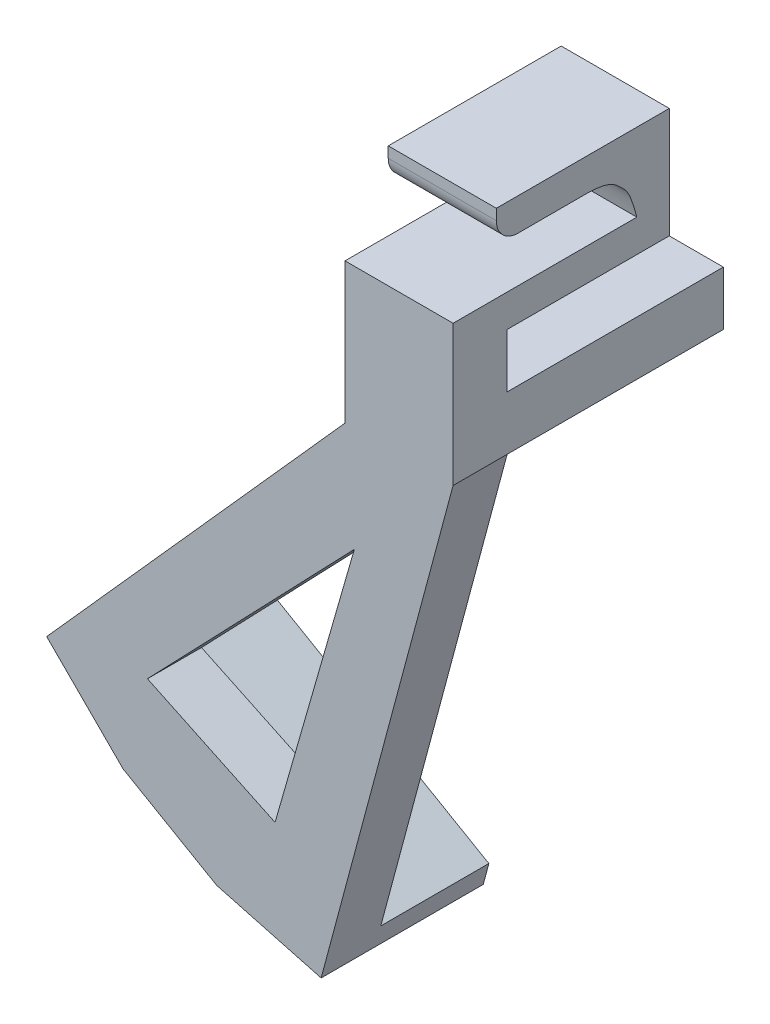
SolidWorks part; units mm, degrees
ref_plane "Front Plane" through (0, 0, 0) normal (0, 0, 1) x (1, 0, 0)
ref_plane "Top Plane" through (0, 0, 0) normal (0, 1, 0) x (1, 0, 0)
ref_plane "Right Plane" through (0, 0, 0) normal (1, 0, 0) x (0, 0, -1)
sketch "Sketch2" plane through (0, 0, 0) normal (1, 0, 0) x (0, 0, -1)
  line L0 (20, 13) -> (20, 20.213)
  line L1 (0, 0) -> (5, 0)
  line L2 (0, 0) -> (0, 13)
  line L3 (0, 13) -> (5, 13)
  line L4 (5, 0) -> (5, 13)
  line L6 (5, 0) -> (5, 3)
  line L9 (5, 13) -> (20, 13)
  line L10 (5, 13) -> (5, 10)
  line L11 (5, 10) -> (20, 10)
  line L12 (20, 13) -> (20, 10)
  line L13 (5, 5) -> (25, 5)
  line L14 (5, 5) -> (5, 0)
  line L15 (5, 0) -> (25, 0)
  line L16 (25, 5) -> (25, 0)
  line L17 (20, 20.213) -> (4, 20.213)
  line L18 (4, 20.213) -> (4, 19.213)
  line L19 (6, 17.213) -> (12.3497, 17.213)
  line L20 (17, 13) -> (20, 13)
  arc A0 (4, 19.213) -> (6, 17.213) centre (6, 19.213) ccw
  spline S0 degree 3 poles (12.3497, 17.213) (14.5346, 17.213) (15.6196, 15.8727) (16.3409, 15.5029) (17, 13) knots 0 0 0 0 0.495489 1 1 1 1
  point P24 (4, 17.213)
  dimension "D3" = 2
  dimension "D16" = 6.9797
  dimension "D1" = 13
  dimension "D2" = 3
  dimension "D4" = 3
  dimension "D5" = 4.213
  dimension "D6" = 5
  dimension "D7" = 3
  dimension "D8" = 5
  dimension "D9" = 15
  dimension "D10" = 20
  dimension "D14" = 2.9866
  dimension "D15" = 4.3328
extrude "Boss-Extrude1" add sketch "Sketch2" along normal blind 10 contours L1 L4 L3 L2 | L4 | L16 L13 L4 L15 | L12 L9 L4 L11 | L19 S0 L9 L0 L17 L18 A0 region at (0, 17.8441, -13.6548) region at (0, 11.5, -12.5) region at (0, 6.5, -2.5) region at (0, 2.5, -15)
sketch "Sketch4" plane through (0, 0, 0) normal (0, 0, 1) x (1, 0, 0)
  line L0 (10, 0) -> (-2.2086, -45.5631)
  line L1 (-2.2086, -45.5631) -> (-11.8678, -42.9749)
  line L2 (-11.8678, -42.9749) -> (-20.5281, -37.9749)
  line L3 (-20.5281, -37.9749) -> (-27.5992, -30.9038)
  line L4 (-27.5992, -30.9038) -> (0, 0)
  line L6 (0, 0) -> (10, 0)
  line L7 (10, 0) -> (0, 0) construction
  line L8 (10, 5) -> (-3.4586, -45.2281) construction
  line L9 (10, 5) -> (0, 5) construction
  line L10 (10, 0) -> (10, 13) construction
  line L11 (-18.2774, -29.6218) -> (-6.4709, -35.2264)
  line L12 (-6.4709, -35.2264) -> (0.8649, -9.6768)
  line L13 (0.8649, -9.6768) -> (-18.2774, -29.6218)
  dimension "D1" = 15
  dimension "D2" = 165
  dimension "D3" = 165
  dimension "D4" = 10
  dimension "D5" = 52
extrude "Boss-Extrude2" add sketch "Sketch4" against normal up to surface (5 mm away) up to face at (5, 7.5, -5)
sketch "Sketch5" plane through (0, 0, -5) normal (0, 0, -1) x (-1, 0, 0)
  line L0 (2.2086, -45.5631) -> (11.8678, -42.9749)
  line L1 (11.8678, -42.9749) -> (20.5281, -37.9749)
  line L2 (20.5281, -37.9749) -> (27.5992, -30.9038)
  line L3 (27.5992, -30.9038) -> (26.267, -29.4121)
  line L4 (27.5992, -30.9038) -> (0, 0) construction
  line L5 (26.267, -29.4121) -> (1.691, -43.6312)
  line L6 (-10, 0) -> (2.2086, -45.5631) construction
  line L7 (1.691, -43.6312) -> (2.2086, -45.5631)
  dimension "D1" = 2
extrude "Boss-Extrude3" add sketch "Sketch5" along normal blind 10
